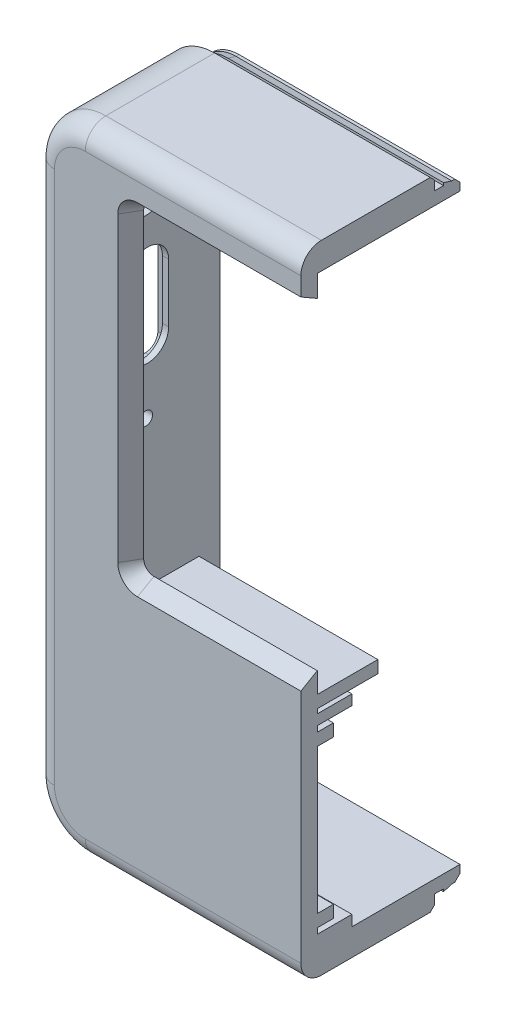
SolidWorks part; units mm, degrees
ref_plane "Front Plane" through (0, 0, 0) normal (0, 0, 1) x (1, 0, 0)
ref_plane "Top Plane" through (0, 0, 0) normal (0, 1, 0) x (1, 0, 0)
ref_plane "Right Plane" through (0, 0, 0) normal (1, 0, 0) x (0, 0, -1)
sketch "Body_Sk1" plane through (0, 0, 0) normal (0, 0, 1) x (1, 0, 0)
  line L0 (-45, -31) -> (45, -31)
  line L1 (50, -26) -> (50, 26)
  line L2 (45, 31) -> (-45, 31)
  line L3 (-50, 26) -> (-50, -26)
  arc A0 (-50, -26) -> (-45, -31) centre (-45, -26) ccw
  arc A1 (45, -31) -> (50, -26) centre (45, -26) ccw
  arc A2 (50, 26) -> (45, 31) centre (45, 26) ccw
  arc A3 (-45, 31) -> (-50, 26) centre (-45, 26) ccw
extrude "Body" add sketch "Body_Sk1" against normal blind 13
fillet "Round_Front" radius 2 8 edges at (-48.5355, -29.5355, 0) (0, -31, 0) (48.5355, -29.5355, 0) (50, 0, 0) (48.5355, 29.5355, 0) (0, 31, 0) (-48.5355, 29.5355, 0) (-50, 0, 0)
ref_plane "PZ_m13_00" through (0, 0, -13) normal (0, 0, 1) x (1, 0, 0)
sketch "Cavity_Sk2" plane through (0, 0, -13) normal (0, 0, 1) x (1, 0, 0)
  line L0 (-45, -28.4) -> (45, -28.4)
  line L1 (47.4, -26) -> (47.4, 26)
  line L2 (45, 28.4) -> (-45, 28.4)
  line L3 (-47.4, 26) -> (-47.4, -26)
  arc A0 (-47.4, -26) -> (-45, -28.4) centre (-45, -26) ccw
  arc A1 (45, -28.4) -> (47.4, -26) centre (45, -26) ccw
  arc A2 (47.4, 26) -> (45, 28.4) centre (45, 26) ccw
  arc A3 (-45, 28.4) -> (-47.4, 26) centre (-45, 26) ccw
extrude "Cavity" cut sketch "Cavity_Sk2" along normal blind 11.4
sketch "Lip_Sk3" plane through (0, 0, -13) normal (0, 0, 1) x (1, 0, 0)
  line L0 (-45, -29.66) -> (45, -29.66)
  line L1 (48.66, -26) -> (48.66, 26)
  line L2 (45, 29.66) -> (-45, 29.66)
  line L3 (-48.66, 26) -> (-48.66, -26)
  line L4 (-45, -28.4) -> (45, -28.4)
  line L5 (47.4, -26) -> (47.4, 26)
  line L6 (45, 28.4) -> (-45, 28.4)
  line L7 (-47.4, 26) -> (-47.4, -26)
  arc A0 (-48.66, -26) -> (-45, -29.66) centre (-45, -26) ccw
  arc A1 (45, -29.66) -> (48.66, -26) centre (45, -26) ccw
  arc A2 (48.66, 26) -> (45, 29.66) centre (45, 26) ccw
  arc A3 (-45, 29.66) -> (-48.66, 26) centre (-45, 26) ccw
  arc A4 (-47.4, -26) -> (-45, -28.4) centre (-45, -26) ccw
  arc A5 (45, -28.4) -> (47.4, -26) centre (45, -26) ccw
  arc A6 (47.4, 26) -> (45, 28.4) centre (45, 26) ccw
  arc A7 (-45, 28.4) -> (-47.4, 26) centre (-45, 26) ccw
extrude "Lip" add sketch "Lip_Sk3" against normal blind 2.5
chamfer "Lip_Chamfer" distance 0.5 angle 45 8 edges at (0, -29.66, -15.5) (48.66, 0, -15.5) (47.588, 28.588, -15.5) (0, 29.66, -15.5) (47.588, -28.588, -15.5) (-47.588, 28.588, -15.5) (-47.588, -28.588, -15.5) (-48.66, 0, -15.5)
ref_plane "PZ_m13_90" through (0, 0, -13.9) normal (0, 0, 1) x (1, 0, 0)
sketch "Bead_Sk4" plane through (0, 0, -13.9) normal (0, 0, 1) x (1, 0, 0)
  line L0 (-45, -29.91) -> (45, -29.91)
  line L1 (48.91, -26) -> (48.91, 26)
  line L2 (45, 29.91) -> (-45, 29.91)
  line L3 (-48.91, 26) -> (-48.91, -26)
  line L4 (-45, -29.06) -> (45, -29.06)
  line L5 (48.06, -26) -> (48.06, 26)
  line L6 (45, 29.06) -> (-45, 29.06)
  line L7 (-48.06, 26) -> (-48.06, -26)
  arc A0 (-48.91, -26) -> (-45, -29.91) centre (-45, -26) ccw
  arc A1 (45, -29.91) -> (48.91, -26) centre (45, -26) ccw
  arc A2 (48.91, 26) -> (45, 29.91) centre (45, 26) ccw
  arc A3 (-45, 29.91) -> (-48.91, 26) centre (-45, 26) ccw
  arc A4 (-48.06, -26) -> (-45, -29.06) centre (-45, -26) ccw
  arc A5 (45, -29.06) -> (48.06, -26) centre (45, -26) ccw
  arc A6 (48.06, 26) -> (45, 29.06) centre (45, 26) ccw
  arc A7 (-45, 29.06) -> (-48.06, 26) centre (-45, 26) ccw
extrude "Bead" add sketch "Bead_Sk4" against normal blind 0.8 draft 17.354
sketch "Screen_Window_Sk5" plane through (0, 0, 0) normal (0, 0, 1) x (1, 0, 0)
  line L0 (-39.91, -6.0338) -> (-0.31, -6.0338)
  line L1 (1.6138, -4.11) -> (1.6138, 25.29)
  line L2 (-0.31, 27.2138) -> (-39.91, 27.2138)
  line L3 (-41.8338, 25.29) -> (-41.8338, -4.11)
  arc A0 (-41.8338, -4.11) -> (-39.91, -6.0338) centre (-39.91, -4.11) ccw
  arc A1 (-0.31, -6.0338) -> (1.6138, -4.11) centre (-0.31, -4.11) ccw
  arc A2 (1.6138, 25.29) -> (-0.31, 27.2138) centre (-0.31, 25.29) ccw
  arc A3 (-39.91, 27.2138) -> (-41.8338, 25.29) centre (-39.91, 25.29) ccw
extrude "Screen_Window" cut sketch "Screen_Window_Sk5" against normal blind 1.9 draft 30
ref_plane "PZ_m1_60" through (0, 0, -1.6) normal (0, 0, 1) x (1, 0, 0)
sketch "Board_Fence_Sk6" plane through (0, 0, -1.6) normal (0, 0, 1) x (1, 0, 0)
  line L0 (2.5, -3.92) -> (3.7, -3.92)
  line L1 (3.7, -3.92) -> (3.7, 27.1)
  line L2 (3.7, 27.1) -> (2.5, 27.1)
  line L3 (2.5, 27.1) -> (2.5, -3.92)
  line L4 (-41.42, -8.32) -> (0.8, -8.32)
  line L5 (0.8, -8.32) -> (0.8, -7.12)
  line L6 (0.8, -7.12) -> (-41.42, -7.12)
  line L7 (-41.42, -7.12) -> (-41.42, -8.32)
extrude "Board_Fence" add sketch "Board_Fence_Sk6" against normal blind 5.9
sketch "TP_Rails_Sk7" plane through (0, 0, -1.6) normal (0, 0, 1) x (1, 0, 0)
  line L0 (-45.7, -26.8) -> (-20.7, -26.8)
  line L1 (-20.7, -26.8) -> (-20.7, -25.6)
  line L2 (-20.7, -25.6) -> (-45.7, -25.6)
  line L3 (-45.7, -25.6) -> (-45.7, -26.8)
  line L4 (-45.7, -11.5) -> (-20.7, -11.5)
  line L5 (-20.7, -11.5) -> (-20.7, -10.3)
  line L6 (-20.7, -10.3) -> (-45.7, -10.3)
  line L7 (-45.7, -10.3) -> (-45.7, -11.5)
extrude "TP_Rails" add sketch "TP_Rails_Sk7" against normal blind 1.57
sketch "TP_Fence_Sk8" plane through (0, 0, -1.6) normal (0, 0, 1) x (1, 0, 0)
  line L0 (-43.2, -9.75) -> (-19.2, -9.75)
  line L1 (-19.2, -9.75) -> (-19.2, -8.75)
  line L2 (-19.2, -8.75) -> (-43.2, -8.75)
  line L3 (-43.2, -8.75) -> (-43.2, -9.75)
  line L4 (-18.9, -26.2) -> (-17.9, -26.2)
  line L5 (-17.9, -26.2) -> (-17.9, -10.9)
  line L6 (-17.9, -10.9) -> (-18.9, -10.9)
  line L7 (-18.9, -10.9) -> (-18.9, -26.2)
  line L8 (-43.2, -28.4) -> (-19.2, -28.4)
  line L9 (-19.2, -28.4) -> (-19.2, -27.35)
  line L10 (-19.2, -27.35) -> (-43.2, -27.35)
  line L11 (-43.2, -27.35) -> (-43.2, -28.4)
extrude "TP_Fence" add sketch "TP_Fence_Sk8" against normal blind 3.37
sketch "Cell_Ribs_Sk9" plane through (0, 0, -1.6) normal (0, 0, 1) x (1, 0, 0)
  line L0 (-10.6, -24.05) -> (-9.4, -24.05)
  line L1 (-9.4, -24.05) -> (-9.4, -12.05)
  line L2 (-9.4, -12.05) -> (-10.6, -12.05)
  line L3 (-10.6, -12.05) -> (-10.6, -24.05)
  line L4 (7.4, -24.05) -> (8.6, -24.05)
  line L5 (8.6, -24.05) -> (8.6, -12.05)
  line L6 (8.6, -12.05) -> (7.4, -12.05)
  line L7 (7.4, -12.05) -> (7.4, -24.05)
  line L8 (21.4, -24.05) -> (22.6, -24.05)
  line L9 (22.6, -24.05) -> (22.6, -12.05)
  line L10 (22.6, -12.05) -> (21.4, -12.05)
  line L11 (21.4, -12.05) -> (21.4, -24.05)
extrude "Cell_Ribs" add sketch "Cell_Ribs_Sk9" against normal blind 9.05
sketch "MAX_Relief_Sk10" plane through (0, 0, -1.6) normal (0, 0, 1) x (1, 0, 0)
  line L0 (20.35, 3.85) -> (37.65, 3.85)
  line L1 (38.65, 4.85) -> (38.65, 17.15)
  line L2 (37.65, 18.15) -> (20.35, 18.15)
  line L3 (19.35, 17.15) -> (19.35, 4.85)
  arc A0 (19.35, 4.85) -> (20.35, 3.85) centre (20.35, 4.85) ccw
  arc A1 (37.65, 3.85) -> (38.65, 4.85) centre (37.65, 4.85) ccw
  arc A2 (38.65, 17.15) -> (37.65, 18.15) centre (37.65, 17.15) ccw
  arc A3 (20.35, 18.15) -> (19.35, 17.15) centre (20.35, 17.15) ccw
extrude "MAX_Relief" cut sketch "MAX_Relief_Sk10" along normal blind 0.9
sketch "MAX_Window_Sk11" plane through (0, 0, 0) normal (0, 0, 1) x (1, 0, 0)
  line L0 (26, 7) -> (32, 7)
  line L1 (34, 9) -> (34, 13)
  line L2 (32, 15) -> (26, 15)
  line L3 (24, 13) -> (24, 9)
  arc A0 (24, 9) -> (26, 7) centre (26, 9) ccw
  arc A1 (32, 7) -> (34, 9) centre (32, 9) ccw
  arc A2 (34, 13) -> (32, 15) centre (32, 13) ccw
  arc A3 (26, 15) -> (24, 13) centre (26, 13) ccw
extrude "MAX_Window" cut sketch "MAX_Window_Sk11" against normal blind 1.8
chamfer "MAX_Window_Chamfer" distance 1 angle 45 8 edges at (24.5858, 7.5858, 0) (29, 7, 0) (33.4142, 7.5858, 0) (34, 11, 0) (33.4142, 14.4142, 0) (29, 15, 0) (24.5858, 14.4142, 0) (24, 11, 0)
ref_plane "PZ_m0_70" through (0, 0, -0.7) normal (0, 0, 1) x (1, 0, 0)
sketch "MAX_Ledges_Sk12" plane through (0, 0, -0.7) normal (0, 0, 1) x (1, 0, 0)
  line L0 (18.65, 3.15) -> (20.25, 3.15)
  line L1 (20.25, 3.15) -> (20.25, 4.75)
  line L2 (20.25, 4.75) -> (18.65, 4.75)
  line L3 (18.65, 4.75) -> (18.65, 3.15)
  line L4 (18.65, 17.25) -> (20.25, 17.25)
  line L5 (20.25, 17.25) -> (20.25, 18.85)
  line L6 (20.25, 18.85) -> (18.65, 18.85)
  line L7 (18.65, 18.85) -> (18.65, 17.25)
  line L8 (37.75, 3.15) -> (39.35, 3.15)
  line L9 (39.35, 3.15) -> (39.35, 4.75)
  line L10 (39.35, 4.75) -> (37.75, 4.75)
  line L11 (37.75, 4.75) -> (37.75, 3.15)
  line L12 (37.75, 17.25) -> (39.35, 17.25)
  line L13 (39.35, 17.25) -> (39.35, 18.85)
  line L14 (39.35, 18.85) -> (37.75, 18.85)
  line L15 (37.75, 18.85) -> (37.75, 17.25)
extrude "MAX_Ledges" add sketch "MAX_Ledges_Sk12" against normal blind 1.3
sketch "MAX_Fence_Sk13" plane through (0, 0, -1.6) normal (0, 0, 1) x (1, 0, 0)
  line L0 (17.45, 20.05) -> (37.35, 20.05)
  line L1 (37.35, 20.05) -> (37.35, 18.85)
  line L2 (37.35, 18.85) -> (18.65, 18.85)
  line L3 (18.65, 18.85) -> (18.65, 3.15)
  line L4 (18.65, 3.15) -> (37.35, 3.15)
  line L5 (37.35, 3.15) -> (37.35, 1.95)
  line L6 (37.35, 1.95) -> (17.45, 1.95)
  line L7 (17.45, 1.95) -> (17.45, 20.05)
extrude "MAX_Fence" add sketch "MAX_Fence_Sk13" against normal blind 2.6
ref_plane "PX_m50_00" through (-50, 0, 0) normal (1, 0, 0) x (0, 0, -1)
sketch "USB_Recess_Sk14" plane through (-50, 0, 0) normal (1, 0, 0) x (0, 0, -1)
  line L0 (12.07, 5.29) -> (12.07, 15.89)
  line L1 (10.87, 17.09) -> (6.07, 17.09)
  line L2 (4.87, 15.89) -> (4.87, 5.29)
  line L3 (6.07, 4.09) -> (10.87, 4.09)
  line L4 (9.6, -23.85) -> (9.6, -13.25)
  line L5 (8.4, -12.05) -> (3.6, -12.05)
  line L6 (2.4, -13.25) -> (2.4, -23.85)
  line L7 (3.6, -25.05) -> (8.4, -25.05)
  arc A0 (10.87, 4.09) -> (12.07, 5.29) centre (10.87, 5.29) ccw
  arc A1 (12.07, 15.89) -> (10.87, 17.09) centre (10.87, 15.89) ccw
  arc A2 (6.07, 17.09) -> (4.87, 15.89) centre (6.07, 15.89) ccw
  arc A3 (4.87, 5.29) -> (6.07, 4.09) centre (6.07, 5.29) ccw
  arc A4 (8.4, -25.05) -> (9.6, -23.85) centre (8.4, -23.85) ccw
  arc A5 (9.6, -13.25) -> (8.4, -12.05) centre (8.4, -13.25) ccw
  arc A6 (3.6, -12.05) -> (2.4, -13.25) centre (3.6, -13.25) ccw
  arc A7 (2.4, -23.85) -> (3.6, -25.05) centre (3.6, -23.85) ccw
extrude "USB_Recess" cut sketch "USB_Recess_Sk14" along normal blind 2
sketch "Left_Ports_Sk15" plane through (-50, 0, 0) normal (1, 0, 0) x (0, 0, -1)
  line L0 (6.42, 7.74) -> (6.42, 13.44)
  line L1 (10.52, 13.44) -> (10.52, 7.74)
  line L2 (3.75, -21.2) -> (3.75, -15.9)
  line L3 (8.25, -15.9) -> (8.25, -21.2)
  arc A0 (6.42, 13.44) -> (10.52, 13.44) centre (8.47, 13.44) cw
  arc A1 (10.52, 7.74) -> (6.42, 7.74) centre (8.47, 7.74) cw
  arc A2 (3.75, -15.9) -> (8.25, -15.9) centre (6, -15.9) cw
  arc A3 (8.25, -21.2) -> (3.75, -21.2) centre (6, -21.2) cw
  circle A4 centre (8.305, 20.04) radius 1.8
  circle A5 centre (8.305, 1.115) radius 0.65
extrude "Left_Ports" cut sketch "Left_Ports_Sk15" along normal blind 3.2
sketch "Buzzer_Keeper_Sk16" plane through (0, 0, -1.6) normal (0, 0, 1) x (1, 0, 0)
  line L0 (44.3, -22) -> (45.5, -22)
  line L1 (45.5, -22) -> (45.5, -14)
  line L2 (45.5, -14) -> (44.3, -14)
  line L3 (44.3, -14) -> (44.3, -22)
extrude "Buzzer_Keeper" add sketch "Buzzer_Keeper_Sk16" against normal blind 14.8
sketch "Mic_Keeper_Sk17" plane through (0, 0, -1.6) normal (0, 0, 1) x (1, 0, 0)
  line L0 (13, 27.2) -> (19, 27.2)
  line L1 (19, 27.2) -> (19, 28.4)
  line L2 (19, 28.4) -> (13, 28.4)
  line L3 (13, 28.4) -> (13, 27.2)
extrude "Mic_Keeper" add sketch "Mic_Keeper_Sk17" against normal blind 13.5
chamfer "Seam_Shadow" distance 0.4 angle 45 8 edges at (0, -31, -13) (50, 0, -13) (48.5355, 29.5355, -13) (0, 31, -13) (48.5355, -29.5355, -13) (-48.5355, 29.5355, -13) (-48.5355, -29.5355, -13) (-50, 0, -13)
ref_plane "PY_m31_00" through (0, -31, 0) normal (0, 1, 0) x (1, 0, 0)
sketch "Pry_Notch_Sk18" plane through (0, -31, 0) normal (0, 1, 0) x (1, 0, 0)
  line L0 (34, 13) -> (42, 13)
  line L1 (42, 13) -> (42, 11.2)
  line L2 (42, 11.2) -> (34, 11.2)
  line L3 (34, 11.2) -> (34, 13)
extrude "Pry_Notch" cut sketch "Pry_Notch_Sk18" along normal blind 1.2
sketch "FitTest_Sk" plane through (0, 0, 0) normal (0, 0, 1) x (1, 0, 0)
  line L0 (-24, -60) -> (96, -60)
  line L1 (96, -60) -> (96, 60)
  line L2 (96, 60) -> (-24, 60)
  line L3 (-24, 60) -> (-24, -60)
extrude "FitTest_Trim" cut sketch "FitTest_Sk" against normal through all and the other way through all
